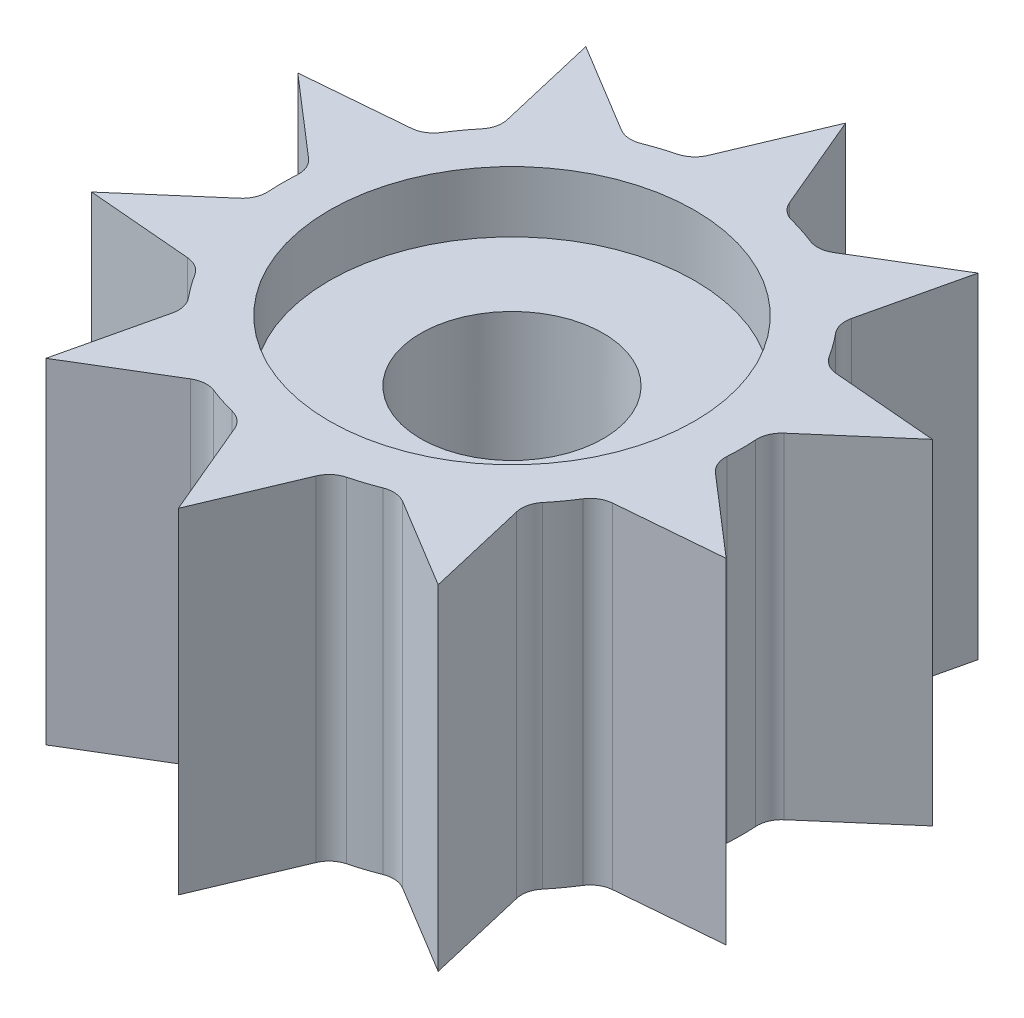
SolidWorks part; units mm, degrees
material "PET"
ref_plane "Front Plane" through (0, 0, 0) normal (0, 0, 1) x (1, 0, 0)
ref_plane "Top Plane" through (0, 0, 0) normal (0, 1, 0) x (1, 0, 0)
ref_plane "Right Plane" through (0, 0, 0) normal (1, 0, 0) x (0, 0, -1)
sketch "Sketch1" plane through (0, 0, 0) normal (0, 1, 0) x (1, 0, 0)
  line L0 (0, 0) -> (0, 7.2373) construction
  line L1 (0, 0) -> (0, -6.8434) construction
  line L2 (0, 0) -> (6.6169, 0) construction
  line L3 (6.6169, 0) -> (-7.4637, 0) construction
  line L4 (0, 5.48) -> (-0.6706, 3.8883)
  line L5 (0, 5.48) -> (0.6706, 3.8883)
  line L8 (3.2211, 4.4334) -> (1.743, 3.5399)
  line L9 (3.2211, 4.4334) -> (2.828, 2.7516)
  line L10 (5.2118, 1.6934) -> (3.4908, 1.8393)
  line L11 (5.2118, 1.6934) -> (3.9052, 0.5638)
  line L12 (5.2118, -1.6934) -> (3.9052, -0.5638)
  line L13 (5.2118, -1.6934) -> (3.4908, -1.8393)
  line L14 (3.2211, -4.4334) -> (2.828, -2.7516)
  line L15 (3.2211, -4.4334) -> (1.743, -3.5399)
  line L16 (0, -5.48) -> (0.6706, -3.8883)
  line L17 (0, -5.48) -> (-0.6706, -3.8883)
  line L18 (-3.2211, -4.4334) -> (-1.743, -3.5399)
  line L19 (-3.2211, -4.4334) -> (-2.828, -2.7516)
  line L20 (-5.2118, -1.6934) -> (-3.4908, -1.8393)
  line L21 (-5.2118, -1.6934) -> (-3.9052, -0.5638)
  line L22 (-5.2118, 1.6934) -> (-3.9052, 0.5638)
  line L23 (-5.2118, 1.6934) -> (-3.4908, 1.8393)
  line L24 (-3.2211, 4.4334) -> (-2.828, 2.7516)
  line L25 (-3.2211, 4.4334) -> (-1.743, 3.5399)
  arc A0 (-0.9396, 3.6562) -> (-1.3889, 3.5102) centre (0, 0) ccw
  circle A1 centre (0, 0) radius 5.48 construction
  arc A2 (0.6706, 3.8883) -> (0.9396, 3.6562) centre (1.0392, 4.0436) ccw
  arc A3 (-0.6706, 3.8883) -> (-0.9396, 3.6562) centre (-1.0392, 4.0436) cw
  arc A4 (2.828, 2.7516) -> (2.9092, 2.4056) centre (3.2175, 2.6605) ccw
  arc A5 (1.743, 3.5399) -> (1.3889, 3.5102) centre (1.5361, 3.8822) cw
  arc A6 (3.9052, 0.5638) -> (3.7676, 0.2362) centre (4.1668, 0.2612) ccw
  arc A7 (3.4908, 1.8393) -> (3.1869, 2.0235) centre (3.5246, 2.2379) cw
  arc A8 (3.4908, -1.8393) -> (3.1869, -2.0235) centre (3.5246, -2.2379) ccw
  arc A9 (3.9052, -0.5638) -> (3.7676, -0.2362) centre (4.1668, -0.2612) cw
  arc A10 (1.743, -3.5399) -> (1.3889, -3.5102) centre (1.5361, -3.8822) ccw
  arc A11 (2.828, -2.7516) -> (2.9092, -2.4056) centre (3.2175, -2.6605) cw
  arc A12 (-0.6706, -3.8883) -> (-0.9396, -3.6562) centre (-1.0392, -4.0436) ccw
  arc A13 (0.6706, -3.8883) -> (0.9396, -3.6562) centre (1.0392, -4.0436) cw
  arc A14 (-2.828, -2.7516) -> (-2.9092, -2.4056) centre (-3.2175, -2.6605) ccw
  arc A15 (-1.743, -3.5399) -> (-1.3889, -3.5102) centre (-1.5361, -3.8822) cw
  arc A16 (-3.9052, -0.5638) -> (-3.7676, -0.2362) centre (-4.1668, -0.2612) ccw
  arc A17 (-3.4908, -1.8393) -> (-3.1869, -2.0235) centre (-3.5246, -2.2379) cw
  arc A18 (-3.4908, 1.8393) -> (-3.1869, 2.0235) centre (-3.5246, 2.2379) ccw
  arc A19 (-3.9052, 0.5638) -> (-3.7676, 0.2362) centre (-4.1668, 0.2612) cw
  arc A20 (-1.743, 3.5399) -> (-1.3889, 3.5102) centre (-1.5361, 3.8822) ccw
  arc A21 (-2.828, 2.7516) -> (-2.9092, 2.4056) centre (-3.2175, 2.6605) cw
  arc A22 (-2.9092, 2.4056) -> (-3.1869, 2.0235) centre (0, 0) ccw
  arc A23 (-3.7676, 0.2362) -> (-3.7676, -0.2362) centre (0, 0) ccw
  arc A24 (-3.1869, -2.0235) -> (-2.9092, -2.4056) centre (0, 0) ccw
  arc A25 (-1.3889, -3.5102) -> (-0.9396, -3.6562) centre (0, 0) ccw
  arc A26 (0.9396, -3.6562) -> (1.3889, -3.5102) centre (0, 0) ccw
  arc A27 (2.9092, -2.4056) -> (3.1869, -2.0235) centre (0, 0) ccw
  arc A28 (3.7676, -0.2362) -> (3.7676, 0.2362) centre (0, 0) ccw
  arc A29 (3.1869, 2.0235) -> (2.9092, 2.4056) centre (0, 0) ccw
  arc A30 (1.3889, 3.5102) -> (0.9396, 3.6562) centre (0, 0) ccw
  point P12 (0.75, 3.6997)
  point P15 (-0.75, 3.6997)
  point P82 (0, 0)
  dimension "D1" = 10.96
  dimension "D2" = 7.55
  dimension "D5" = 0.4
  dimension "D3" = 1.5
  dimension "D4" = 22.845
extrude "Boss-Extrude1" add sketch "Sketch1" along normal blind 5.5
sketch "Sketch2" plane through (0, 5.5, 0) normal (0, 1, 0) x (1, 0, 0)
  circle A0 centre (0, 0) radius 1.5
  circle A1 centre (0, 0) radius 3
  dimension "D1" = 3
  dimension "D2" = 6
extrude "Cut-Extrude2" cut sketch "Sketch2" against normal through all contours A0
extrude "Cut-Extrude3" cut sketch "Sketch2<4>" against normal blind 1
sketch "Sketch2<4>" plane through (0, 5.5, 0) normal (0, 1, 0) x (1, 0, 0) same geometry as "Sketch2"
sketch "Sketch4" plane through (0, 0, 0) normal (0, -1, 0) x (1, 0, 0)
  circle A0 centre (0, 0) radius 3
  dimension "D1" = 6
extrude "Cut-Extrude4" cut sketch "Sketch4" against normal blind 1
sketch "Sketch5" plane through (0, 0, 0) normal (0, -1, 0) x (1, 0, 0)
  circle A0 centre (0, 0) radius 5
  dimension "D1" = 10
